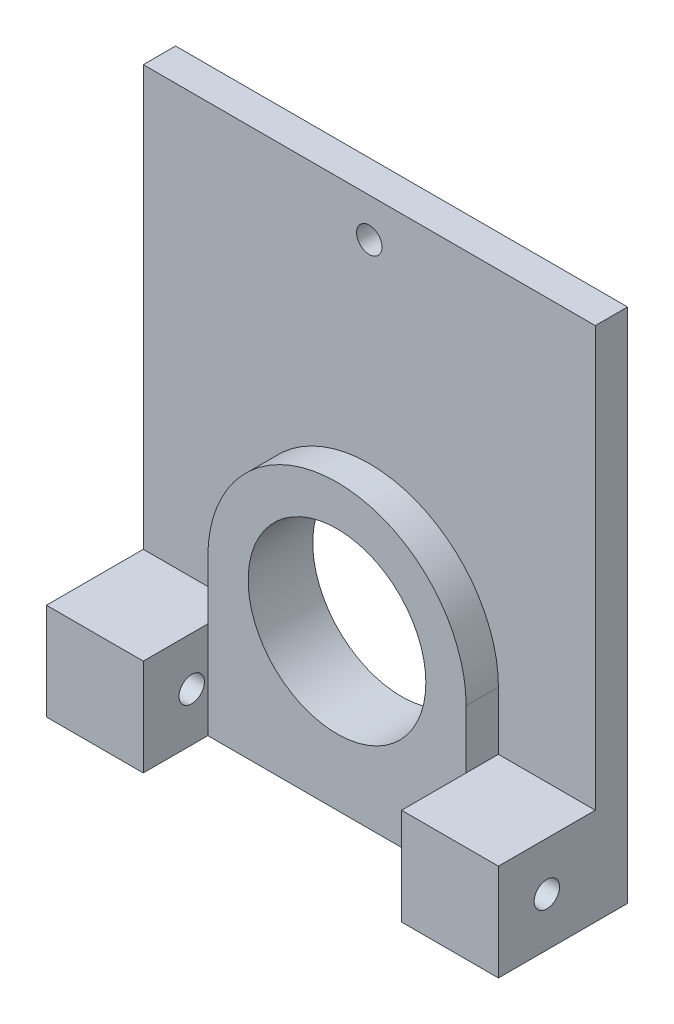
SolidWorks part; units mm, degrees
material "6061 Alloy"
ref_plane "Front Plane" through (0, 0, 0) normal (0, 0, 1) x (1, 0, 0)
ref_plane "Top Plane" through (0, 0, 0) normal (0, 1, 0) x (1, 0, 0)
ref_plane "Right Plane" through (0, 0, 0) normal (1, 0, 0) x (0, 0, -1)
sketch "Sketch1" plane through (0, 0, 0) normal (0, 0, 1) x (1, 0, 0)
  line L1 (-22.225, 25.4) -> (22.225, 25.4)
  line L2 (-22.225, 25.4) -> (-22.225, -25.4)
  line L3 (-22.225, -25.4) -> (22.225, -25.4)
  line L4 (22.225, 25.4) -> (22.225, -25.4)
  line L5 (-22.225, 25.4) -> (22.225, -25.4) construction
  line L6 (-22.225, -25.4) -> (22.225, 25.4) construction
  point P0 (0, 0)
  dimension "D1" = 44.45
  dimension "D2" = 50.8
extrude "Boss-Extrude1" add sketch "Sketch1" along normal blind 3.175
sketch "Sketch2" plane through (0, 0, 3.175) normal (0, 0, 1) x (1, 0, 0)
  line L0 (-12.7, -10.16) -> (-12.7, -25.4)
  line L1 (-22.225, -25.4) -> (22.225, -25.4) construction
  line L2 (12.7, -10.16) -> (12.7, -25.4)
  line L3 (-12.7, -25.4) -> (12.7, -25.4)
  arc A0 (12.7, -10.16) -> (-12.7, -10.16) centre (0, -10.16) ccw
  dimension "D1" = 25.4
  dimension "D2" = 15.24
extrude "Boss-Extrude2" add sketch "Sketch2" along normal blind 3.175
sketch "Sketch3" plane through (0, 0, 3.175) normal (0, 0, 1) x (1, 0, 0)
  line L0 (0, 0) -> (0, -25.4) construction
  line L1 (-22.225, -25.4) -> (-12.7, -25.4)
  line L2 (-22.225, -25.4) -> (-22.225, -15.875)
  line L3 (-22.225, -15.875) -> (-12.7, -15.875)
  line L4 (-12.7, -25.4) -> (-12.7, -15.875)
  line L5 (12.7, -25.4) -> (12.7, -15.875)
  line L6 (22.225, -15.875) -> (12.7, -15.875)
  line L7 (22.225, -25.4) -> (22.225, -15.875)
  line L8 (22.225, -25.4) -> (12.7, -25.4)
  line L9 (-12.7, -10.16) -> (-12.7, -25.4) construction
  dimension "D2" = 9.525
extrude "Boss-Extrude3" add sketch "Sketch3" along normal blind 9.525
sketch "Sketch4" plane through (0, 0, 6.35) normal (0, 0, 1) x (1, 0, 0)
  circle A0 centre (0, -10.16) radius 8.7376
  dimension "D1" = 17.4752
extrude "Cut-Extrude1" cut sketch "Sketch4" against normal through all
sketch "Sketch5" plane through (-22.225, 0, 0) normal (-1, 0, 0) x (0, 0, 1)
  line L0 (3.175, -15.875) -> (12.7, -25.4) construction
sketch "Sketch6" plane through (22.225, 0, 0) normal (1, 0, 0) x (0, 0, -1)
  line L0 (-3.175, -15.875) -> (-12.7, -25.4) construction
sketch "Sketch10" plane through (0, 0, 3.175) normal (0, 0, 1) x (1, 0, 0)
  line L0 (0, 2.54) -> (0, 25.4) construction
  line L1 (22.225, 25.4) -> (-22.225, 25.4) construction
  arc A0 (12.7, -10.16) -> (-12.7, -10.16) centre (0, -10.16) ccw construction
  circle A1 centre (0, -10.16) radius 8.7376 construction
  point P7 (0, 21.59)
  dimension "D1" = 31.75
hole_wizard "M3x0.5 Tapped Hole1" positions "3DSketch1" profile "Sketch8" tap size "M3x0.5" standard "ANSI Metric" end condition up to next
sketch3d "3DSketch1"
  line L0 (22.225, -15.875, 3.175) -> (22.225, -25.4, 12.7) construction
  line L1 (-22.225, -15.875, 3.175) -> (-22.225, -25.4, 12.7) construction
  point P0 (22.225, -20.6375, 7.9375)
  point P4 (-22.225, -20.6375, 7.9375)
  point P10 (0, 21.59, 3.175)
sketch "Sketch8" plane through (22.225, -20.6375, 7.9375) normal (0, 1, 0) x (0, 0, -1)
  line L0 (0, 0) -> (0, 9.525)
  line L1 (0, 9.525) -> (1.25, 9.525)
  line L2 (1.25, 9.525) -> (1.25, 0)
  line L5 (1.25, 0) -> (0, 0)
  line L11 (0, -6.35) -> (0, 107.95) construction
  dimension "Thru Tap Drill Dia." = 2.5
  dimension "Thru Tap Drill Depth" = 9.525
cosmetic thread "Hole Thread4" parameters "D1"=6.35, "D2"=3
cosmetic thread "Hole Thread5" parameters "D1"=6.35, "D2"=3
cosmetic thread "Hole Thread6" parameters "D1"=6.35, "D2"=3
